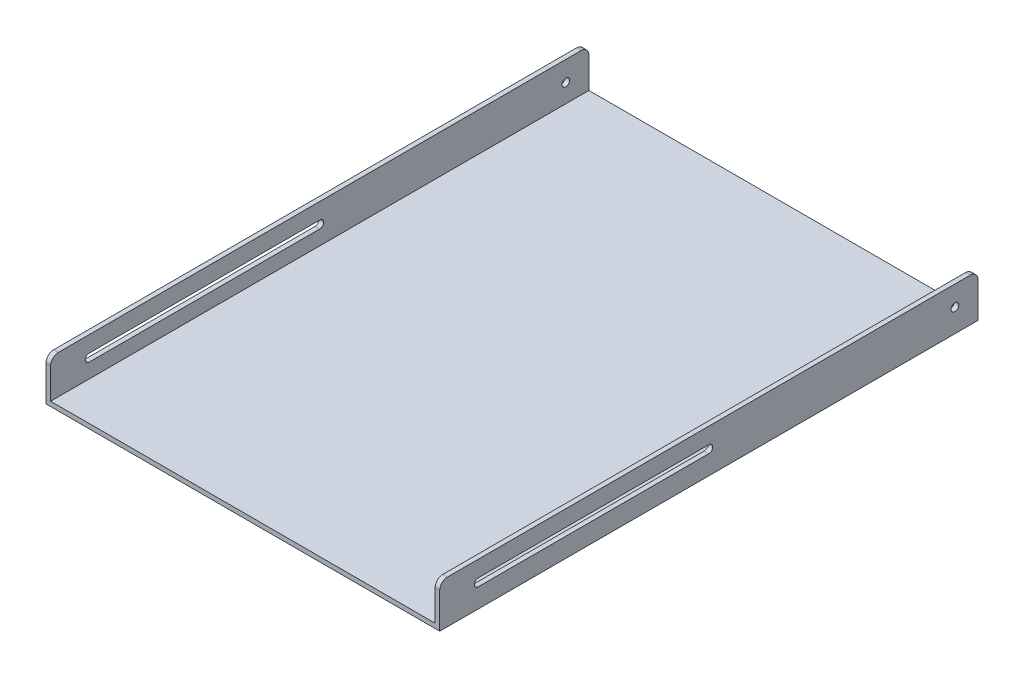
SolidWorks part; units mm, degrees
ref_plane "Front Plane" through (0, 0, 0) normal (0, 0, 1) x (1, 0, 0)
ref_plane "Top Plane" through (0, 0, 0) normal (0, 1, 0) x (1, 0, 0)
ref_plane "Right Plane" through (0, 0, 0) normal (1, 0, 0) x (0, 0, -1)
sketch "Sketch1" plane through (0, 0, 0) normal (0, 0, 1) x (1, 0, 0)
  line L0 (-250, 50) -> (-250, 0)
  line L1 (-250, 0) -> (250, 0)
  line L2 (250, 0) -> (250, 50)
  dimension "D1" = 500
  dimension "D2" = 50
  dimension "D3" = 50
  dimension "D4" = 250
extrude "Extrude-Thin1" add sketch "Sketch1" along normal mid plane 700 thin thin type one direction wall 6
sketch "Sketch2" plane through (256, 0, 0) normal (1, 0, 0) x (0, 0, -1)
  line L0 (350, -6) -> (350, 50) construction
  line L1 (-350, -6) -> (350, -6) construction
  line L2 (-300, 24) -> (0, 24) construction
  line L3 (-300, 29) -> (0, 29)
  line L4 (-300, 19) -> (0, 19)
  circle A0 centre (320, 24) radius 5
  arc A1 (-300, 29) -> (-300, 19) centre (-300, 24) ccw
  arc A2 (0, 19) -> (0, 29) centre (0, 24) ccw
  point P4 (350, 22)
  point P9 (-150, 24)
  dimension "D1" = 10
  dimension "D2" = 30
  dimension "D3" = 30
  dimension "D4" = 150
  dimension "D5" = 300
  dimension "D6" = 10
extrude "Cut-Extrude1" cut sketch "Sketch2" against normal through all
fillet "Fillet1" radius 10 4 edges at (253, 50, 350) (-253, 50, 350) (-253, 50, -350) (253, 50, -350)
ref_plane "Plane1" through (-256, 0, 0) normal (-1, 0, 0) x (0, 0, 1)
sketch "Sketch3" plane through (-256, 0, 0) normal (-1, 0, 0) x (0, 0, 1)
  arc A0 (0, 29) -> (0, 19) centre (0, 24) ccw construction
  arc A1 (0, 29) -> (0, 19) centre (0, 24) ccw
ref_axis "base_prismatic" through (-256, 24, 0) along (0, 0, 1)
